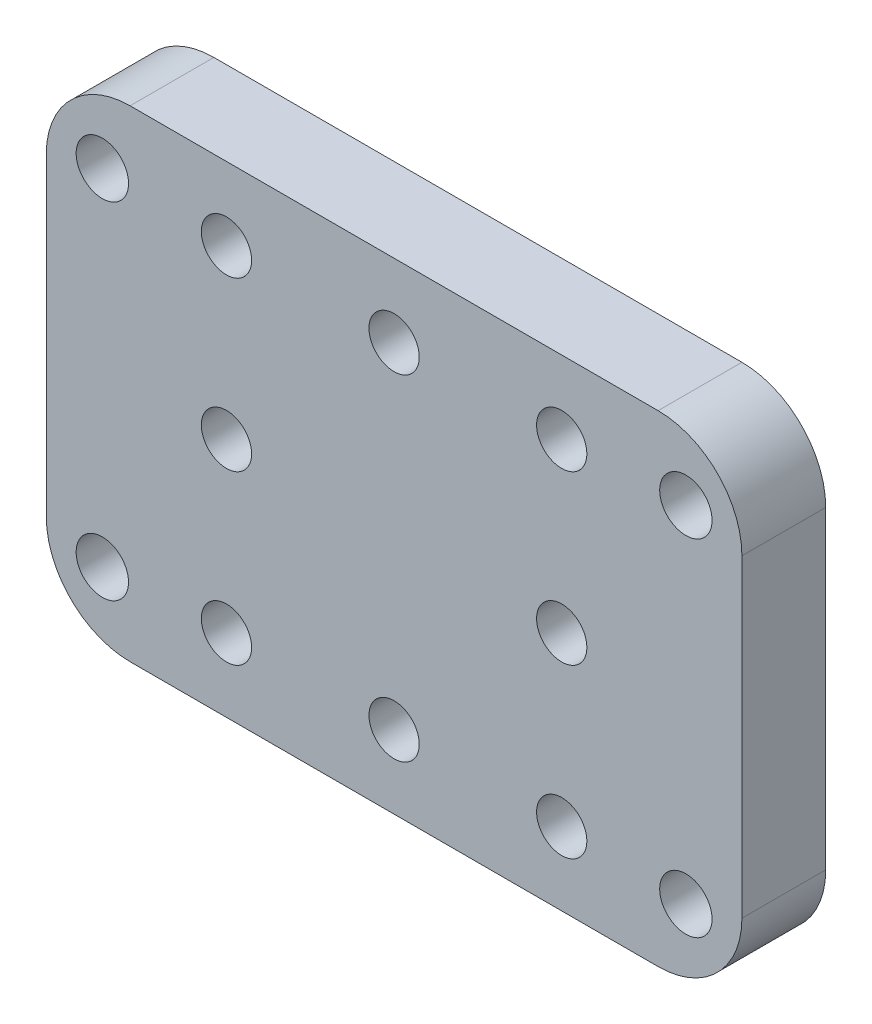
SolidWorks part; units mm, degrees
ref_plane "Alzado" through (0, 0, 0) normal (0, 0, 1) x (1, 0, 0)
ref_plane "Planta" through (0, 0, 0) normal (0, 1, 0) x (1, 0, 0)
ref_plane "Vista lateral" through (0, 0, 0) normal (1, 0, 0) x (0, 0, -1)
sketch "Croquis1" plane through (0, 0, 0) normal (0, 0, 1) x (1, 0, 0)
  line L0 (-0.0106, 23.1539) -> (33.1904, 23.1539)
  line L5 (-0.0106, 23.1539) -> (-0.0106, 0.1756)
  line L6 (-0.0106, 0.1756) -> (33.1904, 0.1756)
  line L7 (33.1904, 23.1539) -> (33.1904, 0.1756)
  circle A0 centre (3.0649, 19.4414) radius 1.3479
  circle A1 centre (30.1148, 19.4414) radius 1.35
  circle A2 centre (30.1148, 3.8881) radius 1.35
  circle A3 centre (3.0649, 3.8881) radius 1.3526
extrude "Saliente-Extruir1" add sketch "Croquis1" along normal blind 4 contours L0 L7 L6 L5
fillet "Redondeo2" radius 4 2 edges at (33.1904, 0.1756, 2) (33.1904, 23.1539, 2)
fillet "Redondeo3" radius 4 2 edges at (-0.0106, 0.1756, 2) (-0.0106, 23.1539, 2)
sketch "Croquis4" plane through (0, 0, 4) normal (0, 0, 1) x (1, 0, 0)
  line L0 (16.5899, 3.6647) -> (16.5899, 0.1756) construction
  line L1 (8.5899, 19.6647) -> (24.5899, 19.6647)
  line L2 (8.5899, 19.6647) -> (8.5899, 3.6647)
  line L3 (8.5899, 3.6647) -> (24.5899, 3.6647)
  line L4 (24.5899, 19.6647) -> (24.5899, 3.6647)
  line L5 (3.9894, 0.1756) -> (29.1904, 0.1756) construction
  line L6 (16.5899, 23.1539) -> (16.5899, 19.6647) construction
  line L7 (24.5899, 11.6647) -> (33.1904, 11.6647) construction
  line L8 (33.1904, 19.1539) -> (33.1904, 4.1756) construction
  line L9 (3.9894, 23.1539) -> (29.1904, 23.1539) construction
  line L10 (8.5899, 11.6647) -> (-0.0106, 11.6647) construction
  line L11 (-0.0106, 19.1539) -> (-0.0106, 4.1756) construction
  circle A0 centre (8.5899, 19.6647) radius 1.2
  circle A1 centre (16.5899, 19.6647) radius 1.2
  circle A2 centre (24.5899, 19.6647) radius 1.2
  circle A3 centre (8.5899, 11.6647) radius 1.2
  circle A4 centre (24.5899, 11.6647) radius 1.2
  circle A5 centre (8.5899, 3.6647) radius 1.2
  circle A6 centre (16.5899, 3.6647) radius 1.2
  circle A7 centre (24.5899, 3.6647) radius 1.2
  dimension "D1" = 16
extrude "Cortar-Extruir3" cut sketch "Croquis4" against normal through all contours L1 A0 L2 | L2 A0 L1 | L2 A3 | L2 A3 | L2 A5 L3 | L3 A5 L2 | L3 A6 | L3 A6 | L3 A7 L4 | L4 A7 L3 | L4 A4 | L4 A4 | L4 A2 L1 | L1 A2 L4 | L1 A1 | L1 A1 region at (8.4201, 19.8345, 4) region at (9.0992, 19.1554, 4) region at (16.5899, 20.174, 4) region at (16.5899, 19.1554, 4) region at (9.0992, 11.6647, 4) region at (8.0806, 11.6647, 4) region at (24.7596, 19.8345, 4) region at (24.0806, 19.1554, 4) region at (9.0992, 4.174, 4) region at (8.4201, 3.495, 4) region at (25.0992, 11.6647, 4) region at (24.0806, 11.6647, 4) region at (16.5899, 4.174, 4) region at (16.5899, 3.1554, 4) region at (24.7596, 3.495, 4) region at (24.0806, 4.174, 4)
sketch3d "Croquis3D2"
  circle A2 centre (2.6649, 3.4247, 13) radius 1.25
  circle A4 centre (2.6649, 19.9047, 13) radius 1.25
  circle A6 centre (30.5149, 3.4247, 13) radius 1.25
  circle A8 centre (30.5149, 19.9047, 13) radius 1.25
  point P7 (2.6649, 3.4247, 14.25)
  point P12 (2.6649, 19.9047, 14.25)
  point P17 (30.5149, 3.4247, 14.25)
  point P22 (30.5149, 19.9047, 14.25)
extrude "Cortar-Extruir4" cut sketch "Croquis3D2" along direction (0, 0, 1) on the side against the normal blind 23
sketch "Croquis5" plane through (0, 0, 0) normal (0, 0, -1) x (-1, 0, 0)
  circle A0 centre (-30.5149, 19.9047) radius 2
  circle A1 centre (-2.6649, 19.9047) radius 2
  circle A2 centre (-30.5149, 3.4247) radius 2
  circle A3 centre (-2.6649, 3.4247) radius 2
extrude "Cortar-Extruir5" cut sketch "Croquis5" against normal blind 2
